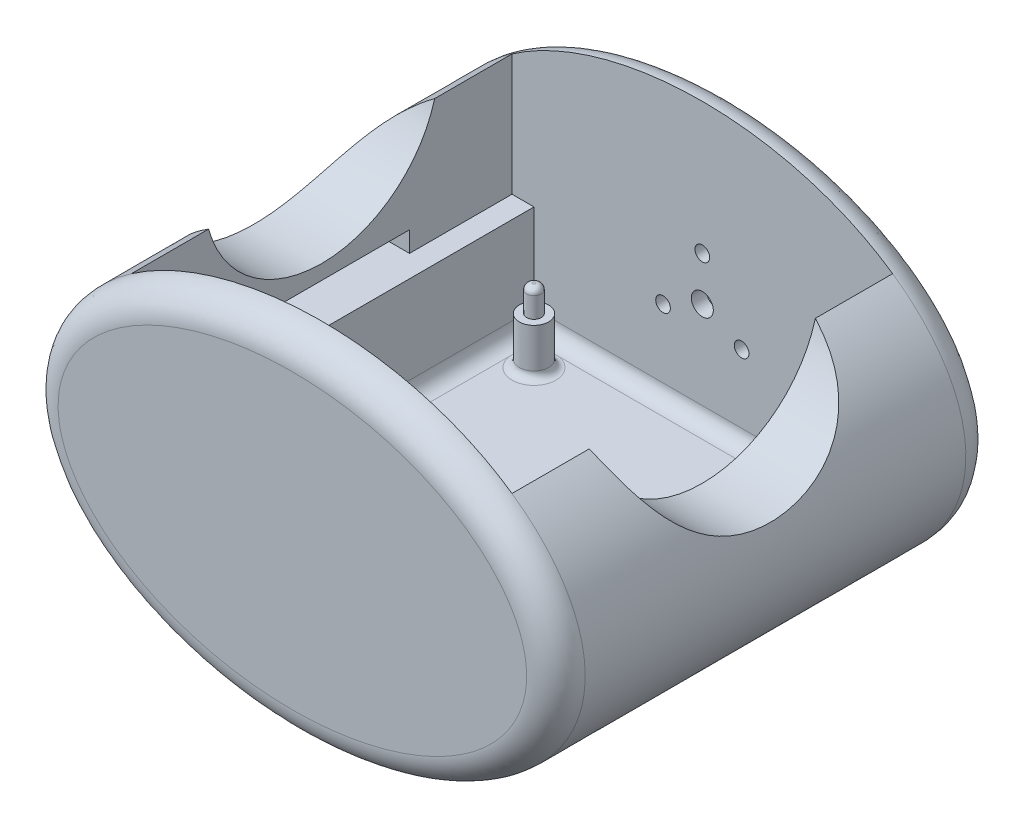
SolidWorks part; units mm, degrees
ref_plane "Front Plane" through (0, 0, 0) normal (0, 0, 1) x (1, 0, 0)
ref_plane "Top Plane" through (0, 0, 0) normal (0, 1, 0) x (1, 0, 0)
ref_plane "Right Plane" through (0, 0, 0) normal (1, 0, 0) x (0, 0, -1)
sketch "Sketch1" plane through (0, 0, 0) normal (0, 0, 1) x (1, 0, 0)
  ellipse E0 centre (0, 0) end of major axis (-22.86, 0) minor radius 15.24
extrude "Boss-Extrude4" add sketch "Sketch1" along normal blind 45.72 contours E0
sketch "Sketch4" plane through (0, 0, 45.72) normal (0, 0, 1) x (1, 0, 0)
  line L1 (14.605, -8.89) -> (-14.605, -8.89)
  line L2 (14.605, -8.89) -> (14.605, 8.89)
  line L3 (14.605, 8.89) -> (-14.605, 8.89)
  line L4 (-14.605, -8.89) -> (-14.605, 8.89)
  dimension "D1" = 8.89
  dimension "D2" = 17.78
  dimension "D3" = 14.605
  dimension "D4" = 29.21
extrude "Cut-Extrude2" cut sketch "Sketch4" against normal blind 33.02 from offset 10.16 offset against normal yes
sketch "Sketch7" plane through (0, 0, 0) normal (1, 0, 0) x (0, 0, -1)
  line L0 (-45.72, 15.24) -> (-45.72, -15.24) construction
  line L1 (-38.1, 16.1024) -> (-52.7439, 16.1024)
  line L2 (-38.1, 16.1024) -> (-38.1, -19.4576)
  line L3 (-38.1, -19.4576) -> (-52.7439, -19.4576)
  line L4 (-52.7439, 16.1024) -> (-52.7439, -19.4576)
  dimension "D1" = 7.62
  dimension "D2" = 14.6439
  dimension "D3" = 35.56
extrude "Cut-Extrude4" cut sketch "Sketch7" against normal blind 33.02 and the other way blind 33.02
sketch "Sketch8" plane through (0, 0, 0) normal (0, 0, 1) x (1, 0, 0)
  circle A0 centre (0, 0) radius 0.9525
  circle A1 centre (3.4078, -1.7039) radius 0.635
  circle A2 centre (-3.4078, -1.7039) radius 0.635
  circle A3 centre (0, 3.81) radius 0.635
  dimension "D1" = 3.81
  dimension "D2" = 1.27
  dimension "D3" = 1.905
  dimension "D4" = 1.27
  dimension "D5" = 1.27
  dimension "D7" = 3.81
  dimension "D8" = 3.81
extrude "Cut-Extrude5" cut sketch "Sketch8" along normal blind 2.54
fillet "Fillet1" radius 2.54 1 edges at (-22.86, 0, 0)
fillet "Fillet2" radius 2.54 1 edges at (-22.86, 0, 38.1)
sketch "Sketch12" plane through (0, 0, 0) normal (0, 0, -1) x (-1, 0, 0)
  line L1 (-16.51, 0) -> (16.51, 0)
  line L2 (-16.51, 0) -> (-16.51, 19.05)
  line L3 (-16.51, 19.05) -> (16.51, 19.05)
  line L4 (16.51, 0) -> (16.51, 19.05)
  dimension "D1" = 33.02
  dimension "D2" = 19.05
  dimension "D3" = 19.05
  dimension "D4" = 16.51
fillet "Fillet3" radius 1.27 4 edges at (-14.605, -8.89, 19.05) (0, -8.89, 2.54) (14.605, -8.89, 19.05) (0, -8.89, 35.56)
sketch "Sketch13" plane through (0, -8.89, 0) normal (0, 1, 0) x (1, 0, 0)
  circle A0 centre (0, -19.05) radius 3.175
  dimension "D8" = 6.35
  dimension "D1" = 19.05
  dimension "D2" = 0
extrude "Cut-Extrude13" cut sketch "Sketch13" against normal through all from offset 2.54 offset against normal yes
sketch "Sketch14" plane through (0, -11.43, 0) normal (0, -1, 0) x (1, 0, 0)
  circle A0 centre (0, 20.955) radius 0.5
  circle A1 centre (0, 17.145) radius 0.5
  dimension "D1" = 1
  dimension "D4" = 1
  dimension "D2" = 20.955
  dimension "D3" = 17.145
extrude "Cut-Extrude14" cut sketch "Sketch14" against normal through all both and the other way through all
extrude "Cut-Extrude16" cut sketch "Sketch12" against normal blind 33.02 from offset 2.54 offset against normal yes
sketch "Sketch17" plane through (16.51, 0, 0) normal (-1, 0, 0) x (0, 0, 1)
  line L0 (35.56, 0) -> (2.54, 0) construction
  line L1 (11.43, 0) -> (26.67, 0)
  line L2 (11.43, 0) -> (11.43, 1.778)
  line L3 (11.43, 1.778) -> (26.67, 1.778)
  line L4 (26.67, 0) -> (26.67, 1.778)
  line L5 (2.54, 10.5409) -> (2.54, 15.24) construction
  dimension "D1" = 1.778
  dimension "D2" = 15.24
  dimension "D3" = 8.89
extrude "Cut-Extrude17" cut sketch "Sketch17" against normal blind 1.778
sketch "Sketch18" plane through (-16.51, 0, 0) normal (1, 0, 0) x (0, 0, -1)
  line L0 (-35.56, 0) -> (-2.54, 0) construction
  line L1 (-26.67, 0) -> (-11.43, 0)
  line L2 (-26.67, 0) -> (-26.67, 1.778)
  line L3 (-26.67, 1.778) -> (-11.43, 1.778)
  line L4 (-11.43, 0) -> (-11.43, 1.778)
  line L5 (-35.56, 10.5409) -> (-35.56, 15.24) construction
  dimension "D1" = 15.24
  dimension "D2" = 8.89
  dimension "D3" = 1.778
extrude "Cut-Extrude18" cut sketch "Sketch18" against normal blind 1.778
sketch "Sketch19" plane through (0, 0, 0) normal (1, 0, 0) x (0, 0, -1)
  line L0 (-35.56, 10.5409) -> (-35.56, -15.24) construction
  line L2 (-26.67, 1.778) -> (-11.43, 1.778) construction
  circle A0 centre (-19.05, 13.208) radius 10.16
  dimension "D1" = 20.32
  dimension "D2" = 16.51
  dimension "D3" = 11.43
extrude "Cut-Extrude19" cut sketch "Sketch19" against normal through all both and the other way through all
sketch "Sketch20" plane through (0, -8.89, 0) normal (0, 1, 0) x (1, 0, 0)
  line L2 (16.51, -35.56) -> (-16.51, -35.56) construction
  line L3 (-14.605, -2.54) -> (-14.605, -35.56) construction
  line L5 (-16.51, -2.54) -> (16.51, -2.54) construction
  line L6 (14.605, -2.54) -> (14.605, -35.56) construction
  circle A0 centre (-11.43, -32.385) radius 1.27
  circle A1 centre (-11.43, -5.715) radius 1.27
  circle A3 centre (11.43, -32.385) radius 1.27
  circle A4 centre (11.43, -5.715) radius 1.27
  circle A5 centre (-11.43, -32.385) radius 0.635
  circle A6 centre (-11.43, -5.715) radius 0.635
  circle A7 centre (11.43, -32.385) radius 0.635
  circle A8 centre (11.43, -5.715) radius 0.635
  dimension "D2" = 2.54
  dimension "D4" = 3.175
  dimension "D5" = 2.54
  dimension "D7" = 2.54
  dimension "D10" = 2.54
  dimension "D13" = 1.27
  dimension "D14" = 1.27
  dimension "D15" = 1.27
  dimension "D16" = 1.27
  dimension "D1" = 3.175
  dimension "D3" = 3.175
  dimension "D6" = 3.175
  dimension "D8" = 3.175
  dimension "D9" = 22.86
  dimension "D11" = 3.175
  dimension "D12" = 26.67
extrude "Boss-Extrude5" add sketch "Sketch20" along normal blind 4.064
sketch "Sketch22" plane through (0, -8.89, 0) normal (0, 1, 0) x (1, 0, 0)
  circle A0 centre (-11.43, -32.385) radius 0.635
  circle A1 centre (-11.43, -5.715) radius 0.635
  circle A2 centre (11.43, -5.715) radius 0.635
  circle A3 centre (11.43, -32.385) radius 0.635
extrude "Boss-Extrude6" add sketch "Sketch22" along normal blind 6.35
fillet "Fillet4" radius 0.635 4 edges at (12.7, -8.89, 5.715) (12.7, -8.89, 32.385) (-10.16, -8.89, 5.715) (-10.16, -8.89, 32.385)
fillet "Fillet5" radius 0.508 4 edges at (-12.065, -2.54, 5.715) (10.795, -2.54, 32.385) (-12.065, -2.54, 32.385) (10.795, -2.54, 5.715)
sketch "Sketch23" plane through (0, 0, 0) normal (0, 0, -1) x (-1, 0, 0)
  circle A0 centre (0, 2.5) radius 2
  circle A1 centre (2.1651, -1.25) radius 2
  circle A3 centre (-2.1651, -1.25) radius 2
  dimension "D1" = 2.5
  dimension "D2" = 4
  dimension "D3" = 4
extrude "Cut-Extrude20" cut sketch "Sketch23" against normal blind 1.27
